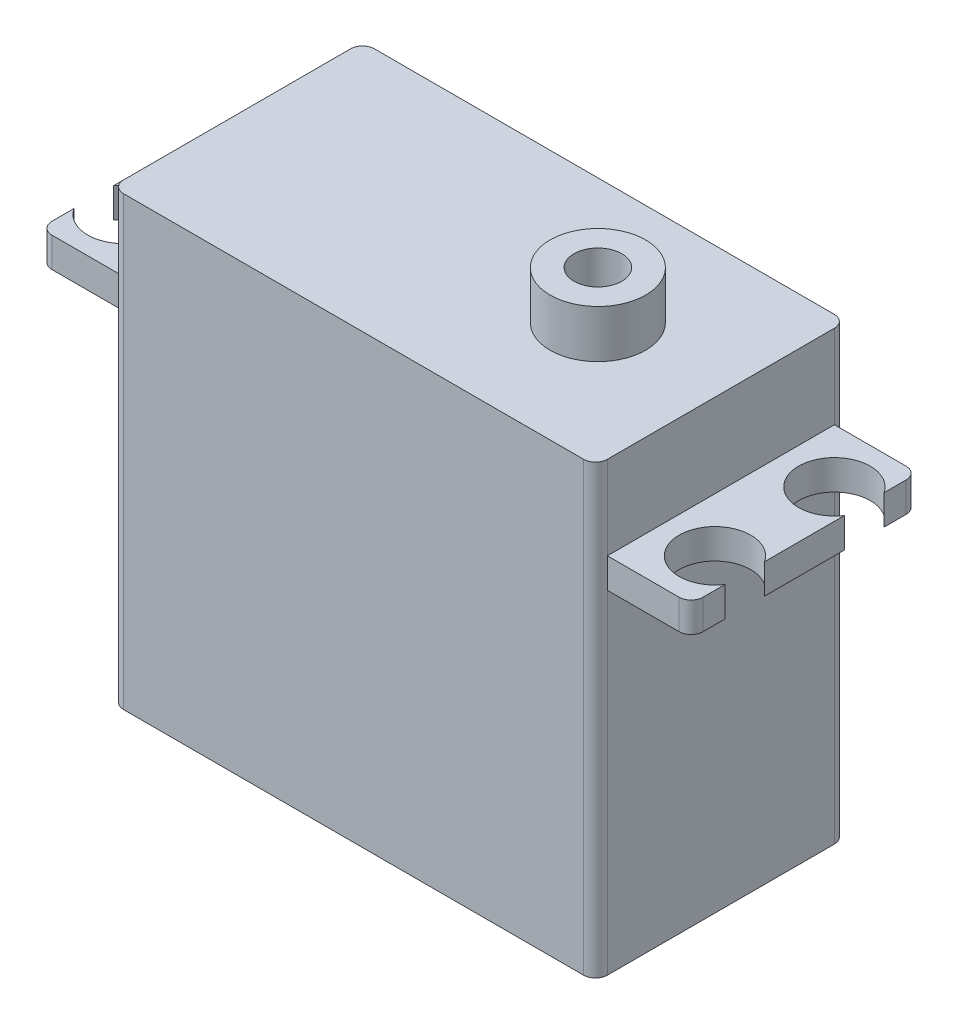
SolidWorks part; units mm, degrees
material "3.0205 (EN-AW 1200)"
ref_plane "Front" through (0, 0, 0) normal (0, 0, 1) x (1, 0, 0)
ref_plane "Top" through (0, 0, 0) normal (0, 1, 0) x (1, 0, 0)
ref_plane "Right" through (0, 0, 0) normal (1, 0, 0) x (0, 0, -1)
sketch "草图1" plane through (0, 0, 0) normal (0, 1, 0) x (1, 0, 0)
  line L0 (0, 0) -> (0, 10.5) construction
  line L1 (-20.25, 10.5) -> (20.25, 10.5) construction
  line L2 (20.25, 10.5) -> (20.25, -10.5) construction
  line L3 (0, 0) -> (20.25, 0) construction
  line L4 (-20.25, 10.5) -> (-20.25, -10.5) construction
  line L5 (-20.25, -10.5) -> (20.25, -10.5) construction
  line L6 (-20.25, -10.5) -> (20.25, -10.5)
  line L7 (20.25, -10.5) -> (20.25, 10.5)
  line L8 (20.25, 10.5) -> (-20.25, 10.5)
  line L9 (-20.25, 10.5) -> (-20.25, -10.5)
  point P9 (-20.25, 0)
extrude "凸台-拉伸1" add sketch "草图1" along normal blind 30.4
sketch "草图2" plane through (20.25, 0, 0) normal (1, 0, 0) x (0, 0, -1)
  line L0 (0, 30.4) -> (0, 27.9) construction
  line L1 (-10.5, 30.4) -> (10.5, 30.4) construction
  line L2 (-9.5, 27.9) -> (9.5, 27.9) construction
  line L3 (-9.5, 27.9) -> (9.5, 27.9)
  line L4 (9.5, 27.9) -> (9.5, 30.4)
  line L5 (9.5, 30.4) -> (-9.5, 30.4)
  line L6 (-9.5, 30.4) -> (-9.5, 27.9)
extrude "凸台-拉伸2" add sketch "草图2" along normal blind 7
sketch "草图3" plane through (0, 30.4, 0) normal (0, 1, 0) x (1, 0, 0)
  line L0 (-20.25, 10.5) -> (-20.25, -10.5)
  line L1 (-20.25, -10.5) -> (20.25, -10.5)
  line L2 (20.25, -10.5) -> (20.25, 10.5)
  line L3 (20.25, 10.5) -> (-20.25, 10.5)
extrude "凸台-拉伸3" add sketch "草图3" along normal blind 7
sketch "草图4" plane through (0, 30.4, 0) normal (0, 1, 0) x (1, 0, 0)
  line L0 (20.25, 0) -> (27.25, 0) construction
  line L1 (20.25, -10.5) -> (20.25, 10.5) construction
  line L2 (27.25, 9.5) -> (27.25, -9.5) construction
  line L3 (20.25, 0) -> (20.25, 5) construction
  line L4 (20.25, -9.5) -> (20.25, 9.5) construction
  line L5 (20.25, 5) -> (24.75, 5) construction
  circle A0 centre (24.75, 5) radius 3
  circle A1 centre (24.75, -5) radius 3
extrude "切除-拉伸1" cut sketch "草图4" against normal blind 7
sketch "草图5" plane through (0, 37.4, 0) normal (0, 1, 0) x (1, 0, 0)
  line L0 (20.25, 0) -> (9.95, 0) construction
  line L1 (20.25, -10.5) -> (20.25, 10.5) construction
  circle A0 centre (9.95, 0) radius 4
  circle A1 centre (9.95, 0) radius 2
extrude "凸台-拉伸4" add sketch "草图5" along normal blind 4
mirror "镜向2" about plane through (0, 0, 0) normal (1, 0, 0) of "切除-拉伸1", "凸台-拉伸2"
fillet "圆角1" radius 1 1 edges at (20.25, 18.7, -10.5)
fillet "圆角2" radius 1 1 edges at (20.25, 18.7, 10.5)
fillet "圆角3" radius 1 1 edges at (-20.25, 18.7, 10.5)
fillet "圆角4" radius 1 1 edges at (-20.25, 18.7, -10.5)
fillet "圆角5" radius 1 1 edges at (-27.25, 29.15, -9.5)
fillet "圆角6" radius 1 1 edges at (-27.25, 29.15, 9.5)
fillet "圆角7" radius 1 1 edges at (27.25, 29.15, 9.5)
fillet "圆角8" radius 1 1 edges at (27.25, 29.15, -9.5)
